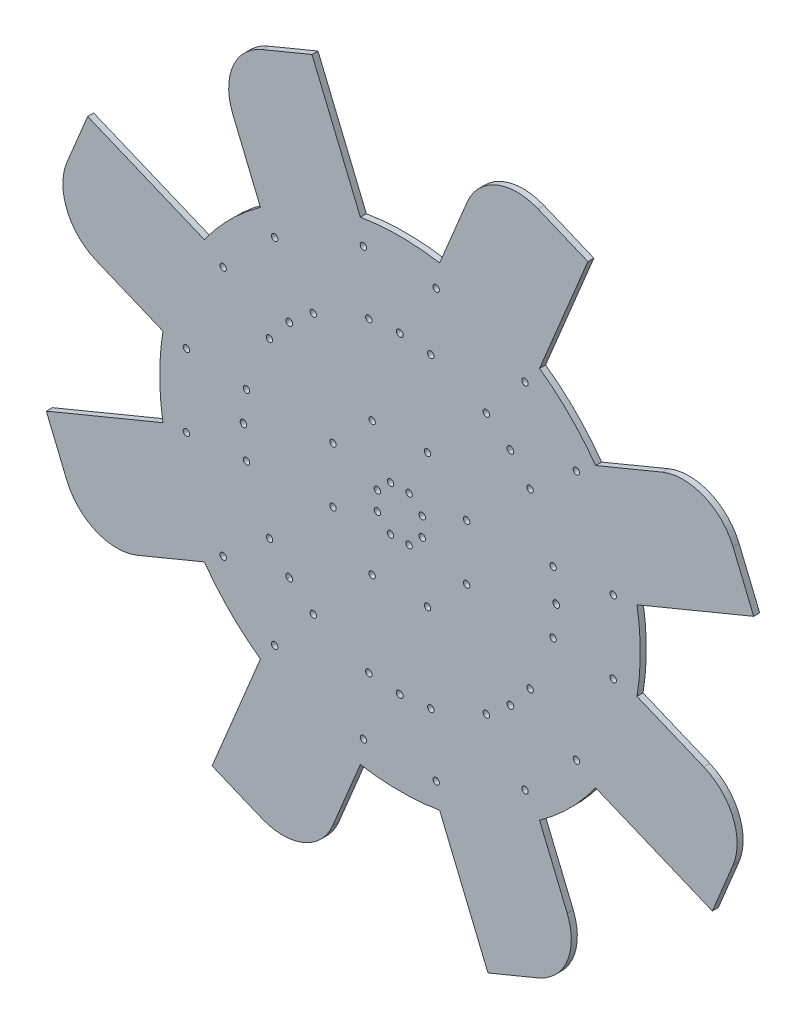
SolidWorks part; units mm, degrees
note: '?' marks a value the reader was unsure of.
ref_plane "Front Plane" through (0, 0, 0) normal (0, 0, 1) x (1, 0, 0)
ref_plane "Top Plane" through (0, 0, 0) normal (0, 1, 0) x (1, 0, 0)
ref_plane "Right Plane" through (0, 0, 0) normal (1, 0, 0) x (0, 0, -1)
sketch "Sketch1" plane through (0, 0, 0) normal (0, 0, 1) x (1, 0, 0)
  circle A0 centre (0, 0) radius 127
  dimension "D1" = 254
extrude "Boss-Extrude1" add sketch "Sketch1" along normal blind 3.175
sketch "Sketch2" plane through (0, 0, 0) normal (0, 0, 1) x (1, 0, 0)
  line L0 (0, 0) -> (117.3327, 48.6008) construction
  circle A0 centre (0, 0) radius 82.55 construction
  circle A1 centre (0, 0) radius 114.3 construction
  point P0 (11.7333, 4.8601)
  point P3 (80.9178, 16.3343)
  point P5 (58.2494, 58.4937)
  point P6 (82.5498, -0.1727)
  point P7 (112.6792, 19.1805)
  point P8 (93.2389, 66.1136)
  point P10 (68.7676, 45.6675)
  point P11 (35.1998, 14.5802)
  dimension "D1" = 12.7
  dimension "D3" = 165.1
  dimension "D4" = 228.6
  dimension "D6" = 31.75
  dimension "D2" = 63.5
  dimension "D5" = 50.8
  dimension "D7" = 38.1
hole_wizard "M3 Clearance Hole1" positions "Sketch3" profile "Sketch4" hole size "M3" standard "ANSI Metric" end condition through all
sketch "Sketch3" plane through (0, 0, 0) normal (0, 0, -1) x (-1, 0, 0)
  point P0 (-58.2494, 58.4937)
  point P3 (-82.5498, -0.1727)
  point P6 (-93.2389, 66.1136)
  point P9 (-112.6792, 19.1805)
  point P12 (-11.7333, 4.8601)
  point P16 (-68.7676, 45.6675)
  point P19 (-80.9178, 16.3343)
  point P22 (-35.1998, 14.5802)
sketch "Sketch4" plane through (58.2494, 58.4937, 0) normal (1, 0, 0) x (0, 1, 0)
  line L0 (0, 0) -> (0, 3.175)
  line L1 (0, 3.175) -> (1.7, 3.175)
  line L2 (1.7, 3.175) -> (1.7, 0)
  line L5 (1.7, 0) -> (0, 0)
  line L11 (0, -6.35) -> (0, 107.95) construction
  dimension "Thru Hole Dia." = 3.4
  dimension "Thru Hole Depth" = 3.175
ref_axis "Axis1" through (0, 0, -0.1588) along (0, 0, 1)?
pattern_circular "CirPattern1" count 8 over 360 about axis through (-0.0975, -0.0404, 0) along (0, 0, 1) of "M3 Clearance Hole1"
sketch "Sketch6" plane through (0, 0, 0) normal (0, 0, -1) x (-1, 0, 0)
  line L1 (-100.5309, 72.5706) -> (-138.664, 88.3659)
  line L2 (-175.9991, 72.9012) -> (-186.9342, 46.5013)
  line L3 (-186.9342, 46.5013) -> (-122.4012, 19.7709)
  line L4 (-122.4012, 19.7709) -> (-100.5309, 72.5706)
  line L5 (0, 0) -> (-117.3327, 48.6008) construction
  arc A0 (-175.9991, 72.9012) -> (-138.664, 88.3659) centre (-149.5992, 61.966) cw
  dimension "D5" = 28.575
  dimension "D1" = 57.15
  dimension "D3" = 190.5
  dimension "D4" = 28.575
extrude "Boss-Extrude2" add sketch "Sketch6" against normal up to surface (3.175 mm away) up to face at (-0.0975, -82.6877, 3.175)
pattern_circular "CirPattern2" count 8 over 360 about axis through (0, 0, 0) along (0, 0, 1) of "Boss-Extrude2"
